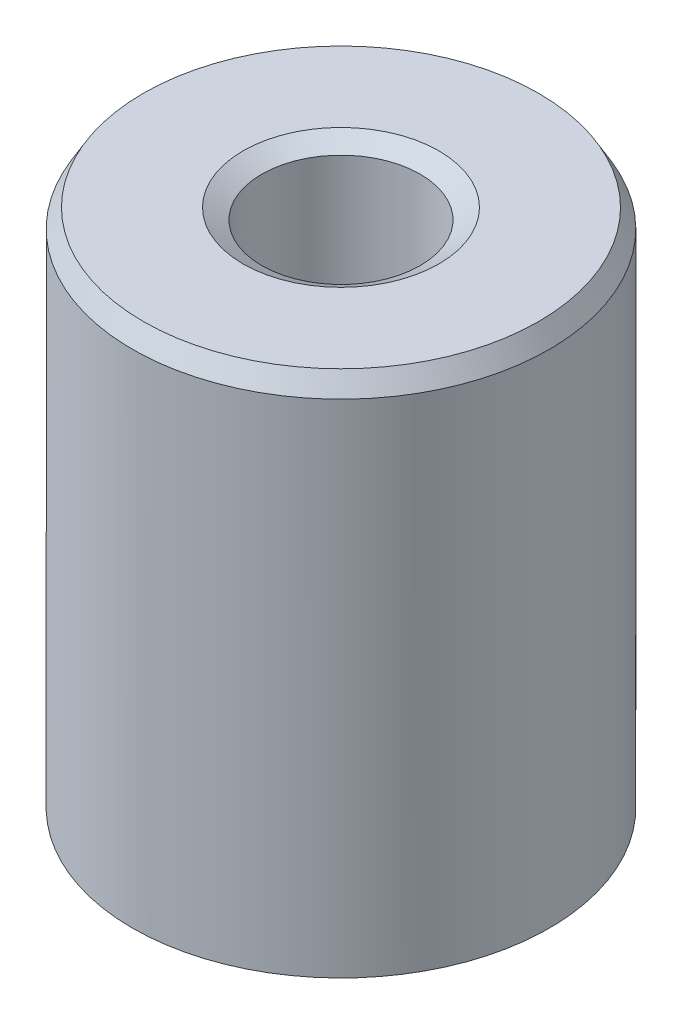
SolidWorks part; units mm, degrees
ref_plane "Front Plane" through (0, 0, 0) normal (0, 0, 1) x (1, 0, 0)
ref_plane "Top Plane" through (0, 0, 0) normal (0, 1, 0) x (1, 0, 0)
ref_plane "Right Plane" through (0, 0, 0) normal (1, 0, 0) x (0, 0, -1)
sketch "Sketch1" plane through (0, 0, 0) normal (0, 1, 0) x (1, 0, 0)
  circle A0 centre (0, 0) radius 15
  dimension "SLEEVE_OD" = 30
extrude "Boss-Extrude1" add sketch "Sketch1" along normal blind 38.1917
sketch "Sketch2" plane through (0, 0, 0) normal (0, 1, 0) x (1, 0, 0)
  circle A0 centre (0, 0) radius 5.7011
  dimension "BORE_D" = 11.4021
extrude "Cut-Extrude1" cut sketch "Sketch2" along normal through all
chamfer "Chamfer1" distance 1.346 angle 30 4 edges at (0, 38.1917, 5.7011) (0, 0, 5.7011) (0, 0, 15) (0, 38.1917, 15) first distance on face at (0, 38.1917, 5.7011) first distance on face at (0, 0, 5.7011) first distance on face at (0, 38.1917, 15)
